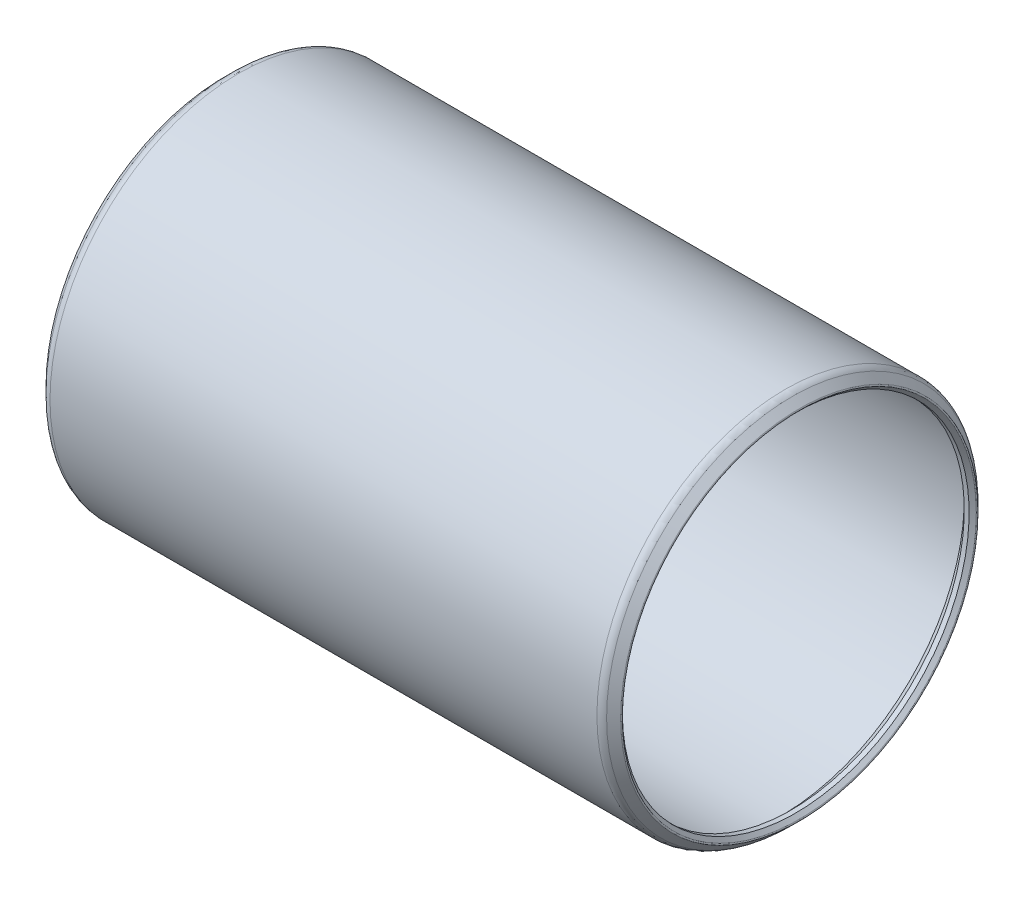
SolidWorks part; units mm, degrees
material "AISI 304"
ref_plane "Front Plane" through (0, 0, 0) normal (0, 0, 1) x (1, 0, 0)
ref_plane "Top Plane" through (0, 0, 0) normal (0, 1, 0) x (1, 0, 0)
ref_plane "Right Plane" through (0, 0, 0) normal (1, 0, 0) x (0, 0, -1)
ref_plane "Plane1" through (58.4835, 0, 0) normal (1, 0, 0) x (0, 0, -1)
sketch "Sketch1" plane through (0, 0, 0) normal (0, 0, 1) x (1, 0, 0)
  line L0 (-0.8826, 18.5547) -> (-0.508, 18.1801)
  line L1 (-0.508, 18.1801) -> (0, 18.1801)
  line L2 (0, 18.1801) -> (1.016, 19.196)
  line L3 (1.016, 19.196) -> (57.4675, 19.196)
  line L4 (57.4675, 19.196) -> (58.4835, 18.1801)
  line L5 (58.4835, 18.1801) -> (58.9915, 18.1801)
  line L6 (58.9915, 18.1801) -> (59.3661, 18.5547)
  line L7 (59.3661, 18.7343) -> (58.6304, 19.47)
  line L8 (57.912, 19.7675) -> (0.5715, 19.7675)
  line L9 (-0.1469, 19.47) -> (-0.8826, 18.7343)
  line L10 (58.4835, 0) -> (0, 0) construction
  arc A0 (-0.8826, 18.7343) -> (-0.8826, 18.5547) centre (-0.7928, 18.6445) ccw
  arc A1 (59.3661, 18.5547) -> (59.3661, 18.7343) centre (59.2763, 18.6445) ccw
  arc A2 (58.6304, 19.47) -> (57.912, 19.7675) centre (57.912, 18.7515) ccw
  arc A3 (0.5715, 19.7675) -> (-0.1469, 19.47) centre (0.5715, 18.7515) ccw
revolve "Revolve1" add sketch "Sketch1" angle 360 about L10 reverse direction yes
ref_plane "Plane2" through (29.2417, 0, 0) normal (1, 0, 0) x (0, 0, -1)
ref_plane "cp1 XY" through (29.2417, 0, 0) normal (1, 0, 0) x (0, 0, -1)
ref_plane "cp1 XZ" through (0, 19.7676, 0) normal (0, -1, 0) x (-1, 0, 0)
ref_plane "cp1 YZ" through (0, 0, 0) normal (0, 0, -1) x (-1, 0, 0)
ref_axis "cp1 X" through (29.2417, 19.7676, 80.9) along (0, 0, -1)
ref_axis "cp1 Y" through (29.2417, -50, 0) along (0, 1, 0)
ref_axis "cp1 Z" through (80.9, 19.7676, 0) along (-1, 0, 0)
sketch3d "cp1"
  point P0 (29.2417, 19.7676, 0)
ref_plane "cp2 XY" through (29.2417, 0, 0) normal (1, 0, 0) x (0, 0, -1)
ref_plane "cp2 XZ" through (0, 0, 0) normal (0, -1, 0) x (-1, 0, 0)
ref_plane "cp2 YZ" through (0, 0, -19.7676) normal (0, 0, -1) x (-1, 0, 0)
ref_axis "cp2 X" through (29.2417, 0, 80.9) along (0, 0, -1)
ref_axis "cp2 Y" through (29.2417, -50, -19.7676) along (0, 1, 0)
ref_axis "cp2 Z" through (80.9, 0, -19.7676) along (-1, 0, 0)
sketch3d "cp2"
  point P0 (29.2417, 0, -19.7676)
ref_plane "cp3 XY" through (29.2417, 0, 0) normal (1, 0, 0) x (0, 0, -1)
ref_plane "cp3 XZ" through (0, -19.7676, 0) normal (0, -1, 0) x (-1, 0, 0)
ref_plane "cp3 YZ" through (0, 0, 0) normal (0, 0, -1) x (-1, 0, 0)
ref_axis "cp3 X" through (29.2417, -19.7676, 80.9) along (0, 0, -1)
ref_axis "cp3 Y" through (29.2417, -50, 0) along (0, 1, 0)
ref_axis "cp3 Z" through (80.9, -19.7676, 0) along (-1, 0, 0)
sketch3d "cp3"
  point P0 (29.2417, -19.7676, 0)
ref_plane "cp4 XY" through (29.2417, 0, 0) normal (1, 0, 0) x (0, 0, -1)
ref_plane "cp4 XZ" through (0, 0, 0) normal (0, -1, 0) x (-1, 0, 0)
ref_plane "cp4 YZ" through (0, 0, 19.7676) normal (0, 0, -1) x (-1, 0, 0)
ref_axis "cp4 X" through (29.2417, 0, 80.9) along (0, 0, -1)
ref_axis "cp4 Y" through (29.2417, -50, 19.7676) along (0, 1, 0)
ref_axis "cp4 Z" through (80.9, 0, 19.7676) along (-1, 0, 0)
sketch3d "cp4"
  point P0 (29.2417, 0, 19.7676)
ref_plane "tube_front XY" through (0, 0, 0) normal (1, 0, 0) x (0, 0, -1)
ref_plane "tube_front XZ" through (0, 0, 0) normal (0, -1, 0) x (-1, 0, 0)
ref_plane "tube_front YZ" through (0, 0, 0) normal (0, 0, -1) x (-1, 0, 0)
ref_axis "tube_front X" through (0, 0, 80.9) along (0, 0, -1)
ref_axis "tube_front Y" through (0, -50, 0) along (0, 1, 0)
ref_axis "tube_front Z" through (80.9, 0, 0) along (-1, 0, 0)
sketch3d "tube_front"
  point P0 (0, 0, 0)
ref_plane "tube_rear XY" through (58.4835, 0, 0) normal (1, 0, 0) x (0, 0, -1)
ref_plane "tube_rear XZ" through (0, 0, 0) normal (0, -1, 0) x (-1, 0, 0)
ref_plane "tube_rear YZ" through (0, 0, 0) normal (0, 0, -1) x (-1, 0, 0)
ref_axis "tube_rear X" through (58.4835, 0, 80.9) along (0, 0, -1)
ref_axis "tube_rear Y" through (58.4835, -50, 0) along (0, 1, 0)
ref_axis "tube_rear Z" through (80.9, 0, 0) along (-1, 0, 0)
sketch3d "tube_rear"
  point P0 (58.4835, 0, 0)
